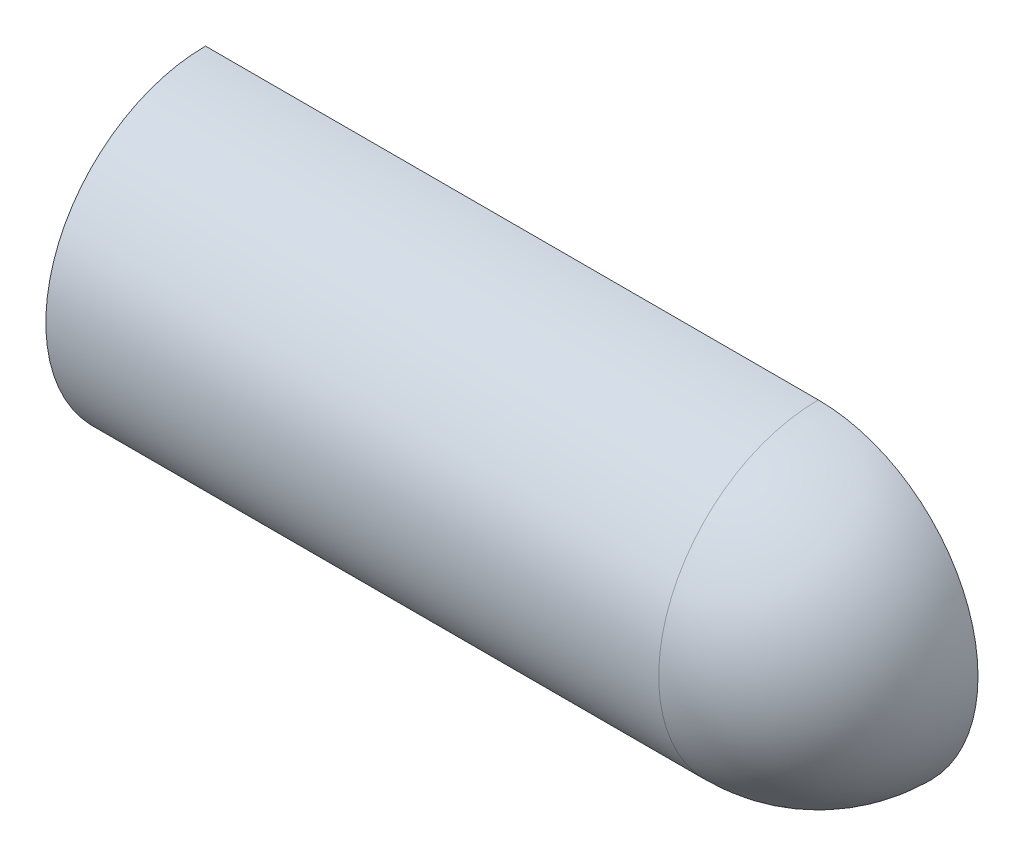
SolidWorks part; units mm, degrees
ref_plane "Front Plane" through (0, 0, 0) normal (0, 0, 1) x (1, 0, 0)
ref_plane "Top Plane" through (0, 0, 0) normal (0, 1, 0) x (1, 0, 0)
ref_plane "Right Plane" through (0, 0, 0) normal (1, 0, 0) x (0, 0, -1)
sketch "Sketch2" plane through (0, 0, 0) normal (0, 0, 1) x (1, 0, 0)
  line L0 (26, 0) -> (31, 0)
  line L2 (-119, 31) -> (0, 31)
  line L3 (-119, 31) -> (-119, 26)
  line L4 (0, 26) -> (-119, 26)
  arc A0 (-8.7283, -29.7459) -> (8.7283, 29.7459) centre (0, 0) ccw construction
  circle A1 centre (0, 0) radius 31 construction
  arc A3 (31, 0) -> (0, 31) centre (0, 0) ccw
  arc A4 (26, 0) -> (0, 26) centre (0, 0) ccw
revolve "Revolve1" add sketch "Sketch2" angle 180 about L0
